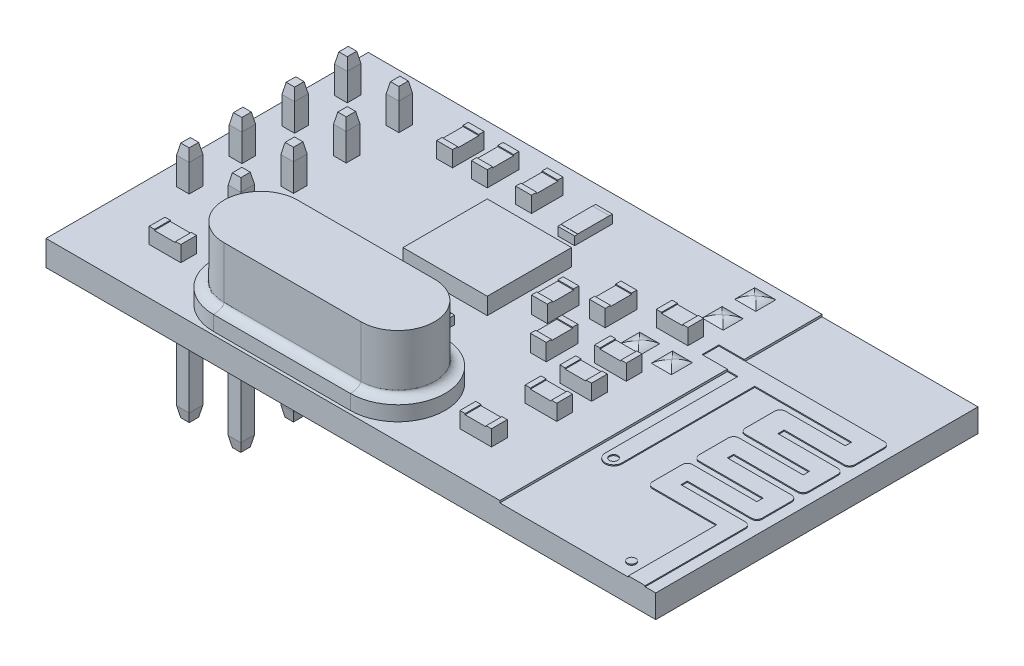
SolidWorks part; units mm, degrees
ref_plane "Plano frontal" through (0, 0, 0) normal (0, 0, 1) x (1, 0, 0)
ref_plane "Plano superior" through (0, 0, 0) normal (0, 1, 0) x (1, 0, 0)
ref_plane "Plano direito" through (0, 0, 0) normal (1, 0, 0) x (0, 0, -1)
sketch "Esboço1" plane through (0, 0, 0) normal (0, 1, 0) x (1, 0, 0)
  line L1 (-14.475, 7.65) -> (14.475, 7.65)
  line L2 (-14.475, 7.65) -> (-14.475, -7.65)
  line L3 (-14.475, -7.65) -> (14.475, -7.65)
  line L4 (14.475, 7.65) -> (14.475, -7.65)
  line L5 (-14.475, 7.65) -> (14.475, -7.65) construction
  line L6 (-14.475, -7.65) -> (14.475, 7.65) construction
  point P0 (0, 0)
  dimension "D1" = 28.95
  dimension "D2" = 15.3
extrude "Ressalto-extrusão1" add sketch "Esboço1" along normal blind 1.2
sketch "Esboço2" plane through (0, 1.2, 0) normal (0, 1, 0) x (1, 0, 0)
  line L0 (-14.475, -7.65) -> (14.475, -7.65) construction
  line L1 (14.475, 7.65) -> (7.075, 7.65)
  line L2 (14.475, 7.65) -> (14.475, -7.65)
  line L3 (14.475, -7.65) -> (7.075, -7.65)
  line L4 (7.075, 7.65) -> (7.075, 3.95)
  line L5 (7.075, 3.95) -> (5.875, 3.95)
  line L6 (5.875, 3.95) -> (5.875, 3.15)
  line L7 (5.875, 3.15) -> (7.075, 3.15)
  line L8 (7.075, 3.15) -> (7.075, -7.65)
  line L9 (14.475, 7.65) -> (-14.475, 7.65) construction
  dimension "D1" = 7.4
  dimension "D2" = 3.7
  dimension "D3" = 0.8
  dimension "D4" = 1.2
extrude "Corte-extrusão1" cut sketch "Esboço2" against normal blind 0.1
sketch "Esboço3" plane through (0, 1.1, 0) normal (0, 1, 0) x (1, 0, 0)
  line L0 (7.075, 3.95) -> (13.975, 3.95)
  line L1 (7.075, 7.65) -> (7.075, 3.95) construction
  line L2 (13.975, 3.95) -> (13.975, 2.05)
  line L3 (13.975, 2.05) -> (10.875, 2.05)
  line L4 (10.875, 2.05) -> (10.875, 1.75)
  line L5 (10.875, 1.75) -> (13.975, 1.75)
  line L6 (13.975, 1.75) -> (13.975, -0.15)
  line L7 (13.975, -0.15) -> (10.675, -0.15)
  line L8 (10.675, -0.15) -> (10.675, -0.45)
  line L9 (10.675, -0.45) -> (13.975, -0.45)
  line L10 (13.975, -0.45) -> (13.975, -2.35)
  line L11 (13.975, -2.35) -> (10.675, -2.35)
  line L12 (10.675, -2.35) -> (10.675, -2.65)
  line L13 (10.675, -2.65) -> (13.975, -2.65)
  line L14 (13.975, -2.65) -> (13.975, -7.65)
  line L15 (7.075, -7.65) -> (14.475, -7.65) construction
  line L16 (13.975, -7.65) -> (13.175, -7.65)
  line L17 (13.175, -7.65) -> (13.175, -3.45)
  line L18 (13.175, -3.45) -> (9.875, -3.45)
  line L19 (9.875, -3.45) -> (9.875, -1.55)
  line L20 (9.875, -1.55) -> (13.175, -1.55)
  line L21 (13.175, -1.55) -> (13.175, -1.25)
  line L22 (13.175, -1.25) -> (9.875, -1.25)
  line L27 (9.875, 0.95) -> (9.875, 2.85)
  line L28 (9.875, 2.85) -> (12.975, 2.85)
  line L29 (12.975, 2.85) -> (12.975, 3.15)
  line L32 (9.875, -1.25) -> (9.875, 0.65)
  line L34 (13.175, 0.65) -> (13.175, 0.95)
  line L35 (7.075, 3.15) -> (7.575, 3.15)
  line L36 (7.575, 3.15) -> (7.575, -3.55)
  line L37 (7.575, -3.55) -> (8.375, -3.55)
  line L38 (8.375, -3.55) -> (8.375, 3.15)
  line L39 (8.375, 3.15) -> (12.975, 3.15)
  line L40 (14.475, 7.65) -> (7.075, 7.65) construction
  line L41 (9.875, 0.65) -> (13.175, 0.65)
  line L42 (9.875, 0.95) -> (13.175, 0.95)
  line L43 (14.475, -7.65) -> (14.475, 7.65) construction
  line L44 (7.075, 7.65) -> (7.075, 3.95) construction
  line L46 (7.075, 3.95) -> (5.875, 3.95)
  line L47 (5.875, 3.95) -> (5.875, 3.15)
  line L48 (5.875, 3.15) -> (7.075, 3.15)
  point P43 (13.175, -1.4)
  dimension "D1" = 3.7
  dimension "D3" = 0.8
  dimension "D4" = 6.7
  dimension "D5" = 0.3
  dimension "D6" = 1.9
  dimension "D7" = 1.9
  dimension "D8" = 0.3
  dimension "D9" = 0.8
  dimension "D10" = 1.9
  dimension "D11" = 0.3
  dimension "D12" = 1.9
  dimension "D13" = 0.3
  dimension "D14" = 0.3
  dimension "D15" = 1.9
  dimension "D16" = 1.9
  dimension "D17" = 0.3
  dimension "D18" = 0.8
  dimension "D19" = 0.5
  dimension "D20" = 0.5
  dimension "D21" = 0.5
  dimension "D22" = 0.5
  dimension "D23" = 1
  dimension "D24" = 0.8
  dimension "D25" = 1
  dimension "D26" = 0.8
  dimension "D27" = 0.8
  dimension "D28" = 0.8
  dimension "D29" = 0.5
  dimension "D30" = 1.5
  dimension "D31" = 1.5
  dimension "D32" = 6.7
extrude "Ressalto-extrusão2" add sketch "Esboço3" along normal blind 0.05
sketch "Esboço4" plane through (0, 1.1, 0) normal (0, 1, 0) x (1, 0, 0)
  line L0 (13.175, -3.45) -> (13.175, -7.65) construction
  line L1 (7.075, -7.65) -> (13.175, -7.65) construction
  circle A0 centre (12.625, -6.95) radius 0.2
  dimension "D1" = 0.4
  dimension "D2" = 0.55
  dimension "D3" = 0.7
extrude "Ressalto-extrusão3" add sketch "Esboço4" along normal blind 0.05
sketch "Esboço5" plane through (0, 1.2, 0) normal (0, 1, 0) x (1, 0, 0)
  line L0 (-6.675, -5.25) -> (-0.175, -5.25) construction
  line L1 (-6.675, -3) -> (-0.175, -3)
  line L2 (-6.675, -7.5) -> (-0.175, -7.5)
  line L3 (-14.475, -7.65) -> (7.075, -7.65) construction
  line L4 (7.075, 3.15) -> (7.075, -7.65) construction
  arc A0 (-6.675, -3) -> (-6.675, -7.5) centre (-6.675, -5.25) ccw
  arc A1 (-0.175, -7.5) -> (-0.175, -3) centre (-0.175, -5.25) ccw
  point P2 (-3.425, -5.25)
  dimension "D3" = 6.5
  dimension "D4" = 7.25
  dimension "D1" = 4.5
  dimension "D2" = 0.15
extrude "Ressalto-extrusão4" add sketch "Esboço5" along normal blind 0.7
sketch "Esboço6" plane through (0, 1.9, 0) normal (0, 1, 0) x (1, 0, 0)
  line L0 (-6.675, -5.25) -> (-0.175, -5.25) construction
  line L1 (-6.675, -3.5) -> (-0.175, -3.5)
  line L2 (-6.675, -7) -> (-0.175, -7)
  line L3 (-6.675, -7.5) -> (-0.175, -7.5) construction
  arc A0 (-6.675, -3.5) -> (-6.675, -7) centre (-6.675, -5.25) ccw
  arc A1 (-0.175, -7) -> (-0.175, -3.5) centre (-0.175, -5.25) ccw
  arc A4 (-6.675, -3) -> (-6.675, -7.5) centre (-6.675, -5.25) ccw construction
  point P2 (-3.425, -5.25)
  point P9 (-3.425, -7.5)
  point P13 (-8.925, -5.25)
  dimension "D2" = 3.5
  dimension "D3" = 0.5
  dimension "D4" = 2.25
  dimension "D1" = 6.5
extrude "Ressalto-extrusão5" add sketch "Esboço6" along normal blind 2.7
sketch "Esboço7" plane through (0, 1.15, 0) normal (0, 1, 0) x (1, 0, 0)
  line L0 (7.575, -3.15) -> (7.575, -3.55)
  line L1 (7.575, -3.55) -> (7.975, -3.55)
  line L2 (7.975, -3.55) -> (8.375, -3.55)
  line L3 (8.375, -3.55) -> (8.375, -3.15)
  arc A0 (7.575, -3.15) -> (8.375, -3.15) centre (7.975, -3.15) ccw
  line M7 (7.575, 3.15) -> (7.575, -3.55)
  line M8 (7.575, -3.55) -> (8.375, -3.55)
  line M9 (8.375, -3.55) -> (8.375, 3.15)
extrude "Corte-extrusão2" cut sketch "Esboço7" against normal blind 0.05 contours A0 M8 M9 | A0 M7 M8
sketch "Esboço8" plane through (0, 1.15, 0) normal (0, 1, 0) x (1, 0, 0)
  circle A0 centre (7.975, -3.15) radius 0.2
  dimension "D1" = 0.4
extrude "Corte-extrusão3" cut sketch "Esboço8" against normal blind 0.05
sketch "Esboço9" plane through (0, 1.2, 0) normal (0, 1, 0) x (1, 0, 0)
  line L0 (-14.475, -7.65) -> (7.075, -7.65) construction
  line L1 (-11.775, -4.7) -> (-10.275, -4.7)
  line L2 (-11.775, -4.7) -> (-11.775, -5.45)
  line L3 (-11.775, -5.45) -> (-10.275, -5.45)
  line L4 (-10.275, -4.7) -> (-10.275, -5.45)
  line L5 (-14.475, 7.65) -> (-14.475, -7.65) construction
  line L6 (7.075, 7.65) -> (-14.475, 7.65) construction
  line L7 (5.875, 3.95) -> (5.875, 3.15) construction
  line L8 (3.175, -4.9) -> (4.675, -4.9)
  line L9 (3.175, -4.9) -> (3.175, -5.65)
  line L10 (3.175, -5.65) -> (4.675, -5.65)
  line L11 (4.675, -4.9) -> (4.675, -5.65)
  line L12 (3.675, -2.3) -> (5.175, -2.3)
  line L13 (3.675, -2.3) -> (3.675, -3.05)
  line L14 (3.675, -3.05) -> (5.175, -3.05)
  line L15 (5.175, -2.3) -> (5.175, -3.05)
  line L16 (3.675, -0.65) -> (5.175, -0.65)
  line L17 (3.675, -0.65) -> (3.675, -1.4)
  line L18 (3.675, -1.4) -> (5.175, -1.4)
  line L19 (5.175, -0.65) -> (5.175, -1.4)
  line L20 (3.675, 1) -> (5.175, 1)
  line L21 (3.675, 1) -> (3.675, 0.25)
  line L22 (3.675, 0.25) -> (5.175, 0.25)
  line L23 (5.175, 1) -> (5.175, 0.25)
  line L24 (3.675, 3.925) -> (5.175, 3.925)
  line L25 (3.675, 3.925) -> (3.675, 3.175)
  line L26 (3.675, 3.175) -> (5.175, 3.175)
  line L27 (5.175, 3.925) -> (5.175, 3.175)
  line L33 (7.075, 3.95) -> (5.875, 3.95) construction
  line L35 (-8.475, 6.4) -> (-7.725, 6.4)
  line L36 (-8.475, 6.4) -> (-8.475, 4.9)
  line L37 (-8.475, 4.9) -> (-7.725, 4.9)
  line L38 (-7.725, 6.4) -> (-7.725, 4.9)
  line L39 (-6.825, 6.4) -> (-6.075, 6.4)
  line L40 (-6.825, 6.4) -> (-6.825, 4.9)
  line L41 (-6.825, 4.9) -> (-6.075, 4.9)
  line L42 (-6.075, 6.4) -> (-6.075, 4.9)
  line L43 (-4.725, 6.4) -> (-3.975, 6.4)
  line L44 (-4.725, 6.4) -> (-4.725, 4.9)
  line L45 (-4.725, 4.9) -> (-3.975, 4.9)
  line L46 (-3.975, 6.4) -> (-3.975, 4.9)
  arc A0 (-6.675, -3) -> (-6.675, -7.5) centre (-6.675, -5.25) ccw construction
  arc A1 (-0.175, -7.5) -> (-0.175, -3) centre (-0.175, -5.25) ccw construction
  point P9 (-8.925, -5.25)
  point P17 (2.075, -5.25)
  point P52 (-6.45, 6.4)
  dimension "D1" = 1.5
  dimension "D2" = 2.2
  dimension "D3" = 1.35
  dimension "D4" = 0.75
  dimension "D5" = 1.5
  dimension "D6" = 0.75
  dimension "D7" = 1.1
  dimension "D8" = 2
  dimension "D9" = 1.85
  dimension "D10" = 0.75
  dimension "D11" = 1.5
  dimension "D12" = 0.9
  dimension "D13" = 0.9
  dimension "D14" = 0.75
  dimension "D15" = 0.75
  dimension "D16" = 1.5
  dimension "D17" = 1.5
  dimension "D18" = 0.75
  dimension "D19" = 1.5
  dimension "D20" = 0.7
  dimension "D21" = 0
  dimension "D22" = 0
  dimension "D23" = 0
  dimension "D24" = 0.025
  dimension "D25" = 0.75
  dimension "D26" = 0.75
  dimension "D27" = 0.75
  dimension "D28" = 1.5
  dimension "D29" = 1.5
  dimension "D30" = 1.5
  dimension "D31" = 6
  dimension "D32" = 0.9
  dimension "D33" = 1.35
  dimension "D34" = 0
  dimension "D35" = 1.25
  dimension "D36" = 1.25
extrude "Ressalto-extrusão6" add sketch "Esboço9" along normal blind 0.75
fillet "Filete1" radius 0.5 4 edges at (-3.425, 1.9, 3.5) (-8.425, 1.9, 5.25) (1.575, 1.9, 5.25) (-3.425, 1.9, 7)
sketch "Esboço10" plane through (0, 0, 0) normal (0, -1, 0) x (1, 0, 0)
  line L0 (-14.475, -7.65) -> (-14.475, 7.65) construction
  line L1 (-14.475, -6.65) -> (-9.475, -6.65)
  line L2 (-14.475, -6.65) -> (-14.475, -4.15)
  line L3 (-14.475, -4.15) -> (-9.475, -4.15)
  line L4 (-9.475, -6.65) -> (-9.475, -4.15)
  line L5 (14.475, -7.65) -> (-14.475, -7.65) construction
  dimension "D1" = 5
  dimension "D2" = 2.5
  dimension "D3" = 1
extrude "Ressalto-extrusão7" add sketch "Esboço10" along normal blind 2.6
chamfer "Chanfro2" distance 0.7092 angle 45 2 edges at (-14.475, -1.3, -4.15) (-9.475, -1.3, -4.15)
sketch "Esboço11" plane through (0, 0, 0) normal (0, -1, 0) x (1, 0, 0)
  line L0 (-14.475, -4.8592) -> (-14.475, 7.65) construction
  line L1 (-14.475, -4.15) -> (-9.475, -4.15)
  line L2 (-14.475, -4.15) -> (-14.475, -1.65)
  line L3 (-14.475, -1.65) -> (-9.475, -1.65)
  line L4 (-9.475, -4.15) -> (-9.475, -1.65)
  dimension "D1" = 2.5
  dimension "D2" = 5
extrude "Ressalto-extrusão8" add sketch "Esboço11" along normal blind 2.6
chamfer "Chanfro3" distance 0.7092 angle 45 2 edges at (-9.475, -1.3, -1.65) (-14.475, -1.3, -1.65)
sketch "Esboço12" plane through (0, 0, 0) normal (0, -1, 0) x (1, 0, 0)
  line L0 (-14.475, -2.3592) -> (-14.475, 7.65) construction
  line L1 (-14.475, -1.65) -> (-9.475, -1.65)
  line L2 (-14.475, -1.65) -> (-14.475, 0.85)
  line L3 (-14.475, 0.85) -> (-9.475, 0.85)
  line L4 (-9.475, -1.65) -> (-9.475, 0.85)
  dimension "D1" = 2.5
  dimension "D2" = 5
extrude "Ressalto-extrusão9" add sketch "Esboço12" along normal blind 2.6
chamfer "Chanfro4" distance 0.7092 angle 45 2 edges at (-9.475, -1.3, 0.85) (-14.475, -1.3, 0.85)
sketch "Esboço13" plane through (0, 0, 0) normal (0, -1, 0) x (1, 0, 0)
  line L0 (-14.475, 0.1408) -> (-14.475, 7.65) construction
  line L1 (-14.475, 0.85) -> (-9.475, 0.85)
  line L2 (-14.475, 0.85) -> (-14.475, 3.35)
  line L3 (-14.475, 3.35) -> (-9.475, 3.35)
  line L4 (-9.475, 0.85) -> (-9.475, 3.35)
  dimension "D1" = 2.5
  dimension "D2" = 5
extrude "Ressalto-extrusão10" add sketch "Esboço13" along normal blind 2.6
chamfer "Chanfro5" distance 0.7092 angle 45 10 edges at (-9.475, -1.3, -6.65) (-14.475, -1.3, -6.65) (-9.475, -1.3, -4.15) (-14.475, -1.3, -4.15) (-9.475, -1.3, -1.65) (-14.475, -1.3, -1.65) (-14.475, -1.3, 0.85) (-9.475, -1.3, 0.85) (-9.475, -1.3, 3.35) (-14.475, -1.3, 3.35)
sketch "Esboço14" plane through (0, -2.6, 0) normal (0, -1, 0) x (1, 0, 0)
  line L0 (-14.475, 2.6408) -> (-14.475, 1.5592) construction
  line L1 (-13.5, 2.425) -> (-12.9, 2.425)
  line L2 (-13.5, 2.425) -> (-13.5, 1.775)
  line L3 (-13.5, 1.775) -> (-12.9, 1.775)
  line L4 (-12.9, 2.425) -> (-12.9, 1.775)
  line L5 (-11.05, 2.425) -> (-10.45, 2.425)
  line L6 (-11.05, 2.425) -> (-11.05, 1.775)
  line L7 (-11.05, 1.775) -> (-10.45, 1.775)
  line L8 (-10.45, 2.425) -> (-10.45, 1.775)
  line L9 (-13.5, -0.075) -> (-12.9, -0.075)
  line L10 (-13.5, -0.075) -> (-13.5, -0.725)
  line L11 (-13.5, -0.725) -> (-12.9, -0.725)
  line L12 (-12.9, -0.075) -> (-12.9, -0.725)
  line L13 (-11.05, -0.075) -> (-10.45, -0.075)
  line L14 (-11.05, -0.075) -> (-11.05, -0.725)
  line L15 (-11.05, -0.725) -> (-10.45, -0.725)
  line L16 (-10.45, -0.075) -> (-10.45, -0.725)
  line L17 (-13.497, -2.575) -> (-12.897, -2.575)
  line L18 (-13.497, -2.575) -> (-13.497, -3.225)
  line L19 (-13.497, -3.225) -> (-12.897, -3.225)
  line L20 (-12.897, -2.575) -> (-12.897, -3.225)
  line L21 (-11.047, -2.575) -> (-10.447, -2.575)
  line L22 (-11.047, -2.575) -> (-11.047, -3.225)
  line L23 (-11.047, -3.225) -> (-10.447, -3.225)
  line L24 (-10.447, -2.575) -> (-10.447, -3.225)
  line L25 (-13.497, -5.075) -> (-12.897, -5.075)
  line L26 (-13.497, -5.075) -> (-13.497, -5.725)
  line L27 (-13.497, -5.725) -> (-12.897, -5.725)
  line L28 (-12.897, -5.075) -> (-12.897, -5.725)
  line L29 (-11.047, -5.075) -> (-10.447, -5.075)
  line L30 (-11.047, -5.075) -> (-11.047, -5.725)
  line L31 (-11.047, -5.725) -> (-10.447, -5.725)
  line L32 (-10.447, -5.075) -> (-10.447, -5.725)
  line L33 (-14.475, 0.1408) -> (-14.475, -0.9408) construction
  line L34 (-10.1842, 3.35) -> (-13.7658, 3.35) construction
  line L35 (-10.1842, 3.35) -> (-13.7658, 3.35) construction
  line L36 (-14.475, -2.3592) -> (-14.475, -3.4408) construction
  line L37 (-14.475, -4.8592) -> (-14.475, -5.9408) construction
  dimension "D1" = 0.6
  dimension "D2" = 0.6
  dimension "D3" = 0.65
  dimension "D4" = 0.65
  dimension "D5" = 1.85
  dimension "D6" = 0.975
  dimension "D7" = 0.975
  dimension "D8" = 1.85
  dimension "D9" = 0.6
  dimension "D10" = 0.6
  dimension "D11" = 0.65
  dimension "D12" = 0.65
  dimension "D13" = 0.925
  dimension "D14" = 0.925
  dimension "D15" = 1.85
  dimension "D16" = 1.85
  dimension "D17" = 1.85
  dimension "D18" = 1.85
  dimension "D19" = 1.85
  dimension "D20" = 1.85
  dimension "D21" = 0.6
  dimension "D22" = 0.65
  dimension "D23" = 0.6
  dimension "D24" = 0.65
  dimension "D25" = 0.6
  dimension "D26" = 0.65
  dimension "D27" = 0.6
  dimension "D28" = 0.65
  dimension "D29" = 1.85
  dimension "D30" = 1.85
  dimension "D31" = 0.978
  dimension "D32" = 0.978
sketch "Esboço15" plane through (0, 1.2, 0) normal (0, 1, 0) x (1, 0, 0)
  line L1 (-0.825, -0.35) -> (-4.825, -0.35)
  line L2 (-0.825, -0.35) -> (-0.825, 3.65)
  line L3 (-0.825, 3.65) -> (-4.825, 3.65)
  line L4 (-4.825, -0.35) -> (-4.825, 3.65)
  line L6 (-4.725, 4.9) -> (-3.975, 4.9) construction
  line L7 (3.675, 1) -> (3.675, 0.25) construction
  dimension "D1" = 4
  dimension "D2" = 4
  dimension "D3" = 1.25
  dimension "D4" = 4.5
extrude "Ressalto-extrusão12" add sketch "Esboço15" along normal blind 0.8
sketch "Esboço16" plane through (0, 1.2, 0) normal (0, 1, 0) x (1, 0, 0)
  line L0 (3.675, -0.65) -> (3.675, -1.4) construction
  line L1 (-1.225, -2.3) -> (-3.025, -2.3)
  line L2 (-1.225, -2.3) -> (-1.225, -1.5)
  line L3 (-1.225, -1.5) -> (-3.025, -1.5)
  line L4 (-3.025, -2.3) -> (-3.025, -1.5)
  line L5 (-4.825, -0.35) -> (-0.825, -0.35) construction
  line L7 (-1.625, 4.6) -> (-2.425, 4.6)
  line L8 (-1.625, 4.6) -> (-1.625, 6.4)
  line L9 (-1.625, 6.4) -> (-2.425, 6.4)
  line L10 (-2.425, 4.6) -> (-2.425, 6.4)
  line L11 (-3.975, 6.4) -> (-4.725, 6.4) construction
  line L12 (-3.975, 4.9) -> (-3.975, 6.4) construction
  dimension "D1" = 0.8
  dimension "D2" = 1.8
  dimension "D3" = 4.9
  dimension "D4" = 1.15
  dimension "D5" = 0.8
  dimension "D6" = 1.8
  dimension "D7" = 0
  dimension "D8" = 1.55
extrude "Ressalto-extrusão13" add sketch "Esboço16" along normal blind 0.4
sketch "Esboço17" plane through (0, 1.2, 0) normal (0, 1, 0) x (1, 0, 0)
  line L0 (3.675, -0.65) -> (3.675, -1.4) construction
  line L1 (0.925, 0.75) -> (0.175, 0.75)
  line L2 (0.925, 0.75) -> (0.925, 2.25)
  line L3 (0.925, 2.25) -> (0.175, 2.25)
  line L4 (0.175, 0.75) -> (0.175, 2.25)
  line L5 (2.475, -0.85) -> (1.725, -0.85)
  line L6 (2.475, -0.85) -> (2.475, 0.65)
  line L7 (2.475, 0.65) -> (1.725, 0.65)
  line L8 (1.725, -0.85) -> (1.725, 0.65)
  line L9 (2.475, 1.95) -> (1.725, 1.95)
  line L10 (2.475, 1.95) -> (2.475, 3.45)
  line L11 (2.475, 3.45) -> (1.725, 3.45)
  line L12 (1.725, 1.95) -> (1.725, 3.45)
  line L13 (3.675, 3.925) -> (3.675, 3.175) construction
  line L14 (7.075, 7.65) -> (-14.475, 7.65) construction
  line L15 (-0.825, -0.35) -> (-0.825, 3.65) construction
  point P20 (0.55, 2.25)
  dimension "D1" = 0.75
  dimension "D2" = 0.75
  dimension "D3" = 0.75
  dimension "D4" = 1.5
  dimension "D5" = 1.5
  dimension "D6" = 1.5
  dimension "D7" = 1.3
  dimension "D8" = 1.2
  dimension "D9" = 1.2
  dimension "D10" = 4.2
  dimension "D11" = 1
  dimension "D12" = 5.4
extrude "Ressalto-extrusão14" add sketch "Esboço17" along normal blind 0.8
sketch "Esboço18" plane through (0, 2, 0) normal (0, 1, 0) x (1, 0, 0)
  line L0 (2.475, -0.85) -> (2.475, 0.65) construction
  line L1 (2.475, -0.6) -> (1.725, -0.6)
  line L2 (2.475, -0.6) -> (2.475, 0.4)
  line L3 (2.475, 0.4) -> (1.725, 0.4)
  line L4 (1.725, -0.6) -> (1.725, 0.4)
  line L5 (1.725, 0.65) -> (1.725, -0.85) construction
  line L6 (0.925, 0.75) -> (0.925, 2.25) construction
  line L7 (0.925, 1) -> (0.175, 1)
  line L8 (0.925, 1) -> (0.925, 2)
  line L9 (0.925, 2) -> (0.175, 2)
  line L10 (0.175, 1) -> (0.175, 2)
  line L11 (0.175, 2.25) -> (0.175, 0.75) construction
  line L12 (2.475, 1.95) -> (2.475, 3.45) construction
  line L13 (2.475, 2.2) -> (1.725, 2.2)
  line L14 (2.475, 2.2) -> (2.475, 3.2)
  line L15 (2.475, 3.2) -> (1.725, 3.2)
  line L16 (1.725, 2.2) -> (1.725, 3.2)
  line L17 (1.725, 3.45) -> (1.725, 1.95) construction
  line L18 (1.725, -0.85) -> (2.475, -0.85) construction
  line L20 (0.175, 0.75) -> (0.925, 0.75) construction
  line L21 (2.475, 3.45) -> (1.725, 3.45) construction
  dimension "D1" = 1
  dimension "D2" = 0.25
  dimension "D3" = 0.25
  dimension "D4" = 1
  dimension "D5" = 1
  dimension "D6" = 0.25
extrude "Corte-extrusão4" cut sketch "Esboço18" against normal blind 0.05
sketch "Esboço19" plane through (0, 1.95, 0) normal (0, 1, 0) x (1, 0, 0)
  line L0 (-3.975, 4.9) -> (-3.975, 6.4) construction
  line L1 (-3.975, 5.15) -> (-4.725, 5.15)
  line L2 (-3.975, 5.15) -> (-3.975, 6.15)
  line L3 (-3.975, 6.15) -> (-4.725, 6.15)
  line L4 (-4.725, 5.15) -> (-4.725, 6.15)
  line L5 (-4.725, 6.4) -> (-4.725, 4.9) construction
  line L6 (-6.075, 4.9) -> (-6.075, 6.4) construction
  line L7 (-6.075, 5.15) -> (-6.825, 5.15)
  line L8 (-6.075, 5.15) -> (-6.075, 6.15)
  line L9 (-6.075, 6.15) -> (-6.825, 6.15)
  line L10 (-6.825, 5.15) -> (-6.825, 6.15)
  line L11 (-6.825, 6.4) -> (-6.825, 4.9) construction
  line L12 (-7.725, 4.9) -> (-7.725, 6.4) construction
  line L13 (-7.725, 5.15) -> (-8.475, 5.15)
  line L14 (-7.725, 5.15) -> (-7.725, 6.15)
  line L15 (-7.725, 6.15) -> (-8.475, 6.15)
  line L16 (-8.475, 5.15) -> (-8.475, 6.15)
  line L17 (-8.475, 6.4) -> (-8.475, 4.9) construction
  line L18 (3.675, 3.175) -> (5.175, 3.175) construction
  line L19 (4.925, 3.175) -> (3.925, 3.175)
  line L20 (4.925, 3.175) -> (4.925, 3.925)
  line L21 (4.925, 3.925) -> (3.925, 3.925)
  line L22 (3.925, 3.175) -> (3.925, 3.925)
  line L23 (5.175, 3.925) -> (3.675, 3.925) construction
  line L24 (3.675, 0.25) -> (5.175, 0.25) construction
  line L25 (4.925, 0.25) -> (3.925, 0.25)
  line L26 (4.925, 0.25) -> (4.925, 1)
  line L27 (4.925, 1) -> (3.925, 1)
  line L28 (3.925, 0.25) -> (3.925, 1)
  line L29 (5.175, 1) -> (3.675, 1) construction
  line L30 (3.675, -1.4) -> (5.175, -1.4) construction
  line L31 (4.925, -1.4) -> (3.925, -1.4)
  line L32 (4.925, -1.4) -> (4.925, -0.65)
  line L33 (4.925, -0.65) -> (3.925, -0.65)
  line L34 (3.925, -1.4) -> (3.925, -0.65)
  line L35 (5.175, -0.65) -> (3.675, -0.65) construction
  line L36 (3.675, -3.05) -> (5.175, -3.05) construction
  line L37 (4.925, -3.05) -> (3.925, -3.05)
  line L38 (4.925, -3.05) -> (4.925, -2.3)
  line L39 (4.925, -2.3) -> (3.925, -2.3)
  line L40 (3.925, -3.05) -> (3.925, -2.3)
  line L41 (5.175, -2.3) -> (3.675, -2.3) construction
  line L42 (3.175, -5.65) -> (4.675, -5.65) construction
  line L43 (4.425, -5.65) -> (3.425, -5.65)
  line L44 (4.425, -5.65) -> (4.425, -4.9)
  line L45 (4.425, -4.9) -> (3.425, -4.9)
  line L46 (3.425, -5.65) -> (3.425, -4.9)
  line L47 (4.675, -4.9) -> (3.175, -4.9) construction
  line L48 (-11.775, -5.45) -> (-10.275, -5.45) construction
  line L49 (-10.525, -5.45) -> (-11.525, -5.45)
  line L50 (-10.525, -5.45) -> (-10.525, -4.7)
  line L51 (-10.525, -4.7) -> (-11.525, -4.7)
  line L52 (-11.525, -5.45) -> (-11.525, -4.7)
  line L53 (-10.275, -4.7) -> (-11.775, -4.7) construction
  line L54 (-11.775, -4.7) -> (-11.775, -5.45) construction
  line L55 (3.175, -4.9) -> (3.175, -5.65) construction
  line L56 (3.675, -2.3) -> (3.675, -3.05) construction
  line L57 (3.675, -0.65) -> (3.675, -1.4) construction
  line L58 (5.175, 0.25) -> (5.175, 1) construction
  line L59 (5.175, 3.175) -> (5.175, 3.925) construction
  line L60 (-4.725, 4.9) -> (-3.975, 4.9) construction
  line L61 (-6.825, 4.9) -> (-6.075, 4.9) construction
  line L62 (-8.475, 4.9) -> (-7.725, 4.9) construction
  dimension "D1" = 1
  dimension "D2" = 0.25
  dimension "D3" = 0.25
  dimension "D4" = 1
  dimension "D5" = 1
  dimension "D6" = 0.25
  dimension "D7" = 1
  dimension "D8" = 0.25
  dimension "D9" = 0.25
  dimension "D10" = 1
  dimension "D11" = 1
  dimension "D12" = 0.25
  dimension "D13" = 0.25
  dimension "D14" = 1
  dimension "D15" = 1
  dimension "D16" = 0.25
  dimension "D17" = 0.25
  dimension "D18" = 1
extrude "Corte-extrusão5" cut sketch "Esboço19" against normal blind 0.05
sketch "Esboço20" plane through (0, 1.6, 0) normal (0, 1, 0) x (1, 0, 0)
  line L0 (-3.025, -2.3) -> (-1.225, -2.3) construction
  line L1 (-1.375, -2.3) -> (-2.875, -2.3)
  line L2 (-1.375, -2.3) -> (-1.375, -1.5)
  line L3 (-1.375, -1.5) -> (-2.875, -1.5)
  line L4 (-2.875, -2.3) -> (-2.875, -1.5)
  line L5 (-1.225, -1.5) -> (-3.025, -1.5) construction
  line L6 (-1.625, 4.6) -> (-1.625, 6.4) construction
  line L7 (-1.625, 4.75) -> (-2.425, 4.75)
  line L8 (-1.625, 4.75) -> (-1.625, 6.25)
  line L9 (-1.625, 6.25) -> (-2.425, 6.25)
  line L10 (-2.425, 4.75) -> (-2.425, 6.25)
  line L11 (-2.425, 6.4) -> (-2.425, 4.6) construction
  line L13 (-3.025, -1.5) -> (-3.025, -2.3) construction
  line L14 (-2.425, 4.6) -> (-1.625, 4.6) construction
  dimension "D1" = 1.5
  dimension "D2" = 0.15
  dimension "D3" = 1.5
  dimension "D4" = 0.15
extrude "Ressalto-extrusão15" add sketch "Esboço20" along normal blind 0.01
sketch "Esboço21" plane through (-14.475, 0, 0) normal (-1, 0, 0) x (0, 0, 1)
  line L1 (2.6408, 0) -> (1.5592, 0)
  line L2 (2.6408, 0) -> (2.6408, -2.6)
  line L3 (2.6408, -2.6) -> (1.5592, -2.6)
  line L4 (1.5592, 0) -> (1.5592, -2.6)
  line L5 (0.1408, 0) -> (-0.9408, 0)
  line L6 (0.1408, 0) -> (0.1408, -2.6)
  line L7 (0.1408, -2.6) -> (-0.9408, -2.6)
  line L8 (-0.9408, 0) -> (-0.9408, -2.6)
  line L9 (-2.3592, 0) -> (-3.4408, 0)
  line L10 (-2.3592, 0) -> (-2.3592, -2.6)
  line L11 (-2.3592, -2.6) -> (-3.4408, -2.6)
  line L12 (-3.4408, 0) -> (-3.4408, -2.6)
  line L13 (-4.8592, 0) -> (-5.9408, 0)
  line L14 (-4.8592, 0) -> (-4.8592, -2.6)
  line L15 (-4.8592, -2.6) -> (-5.9408, -2.6)
  line L16 (-5.9408, 0) -> (-5.9408, -2.6)
extrude "Corte-extrusão6" cut sketch "Esboço21" against normal blind 0.001
sketch "Esboço22" plane through (0, 0, -6.65) normal (0, 0, -1) x (-1, 0, 0)
  line L0 (13.7658, 0) -> (10.1842, 0) construction
  line L1 (13.4742, 0) -> (10.4742, 0)
  line L2 (13.4742, 0) -> (13.4742, -1)
  line L3 (13.4742, -1) -> (10.4742, -1)
  line L4 (10.4742, 0) -> (10.4742, -1)
  line L5 (10.1842, 0) -> (10.1842, -2.6) construction
  dimension "D1" = 3
  dimension "D2" = 1
  dimension "D3" = 0.29
extrude "Corte-extrusão7" cut sketch "Esboço22" against normal through all
extrude "Ressalto-extrusão16" add sketch "Esboço14" along normal blind 5.7 and the other way blind 5.6
chamfer "Chanfro8" distance 0.5 distance2 0.1 32 edges at (-10.75, -8.3, 2.425) (-10.45, -8.3, 2.1) (-10.75, -8.3, 1.775) (-11.05, -8.3, 2.1) (-13.2, -8.3, 2.425) (-12.9, -8.3, 2.1) (-13.2, -8.3, 1.775) (-13.5, -8.3, 2.1) (-13.2, -8.3, -0.075) (-12.9, -8.3, -0.4) (-13.2, -8.3, -0.725) (-13.5, -8.3, -0.4) (-10.75, -8.3, -0.075) (-10.45, -8.3, -0.4) (-10.75, -8.3, -0.725) (-11.05, -8.3, -0.4) (-10.747, -8.3, -2.575) (-10.447, -8.3, -2.9) (-10.747, -8.3, -3.225) (-11.047, -8.3, -2.9) (-13.197, -8.3, -2.575) (-12.897, -8.3, -2.9) (-13.197, -8.3, -3.225) (-13.497, -8.3, -2.9) (-10.747, -8.3, -5.075) (-10.447, -8.3, -5.4) (-10.747, -8.3, -5.725) (-11.047, -8.3, -5.4) (-13.197, -8.3, -5.075) (-12.897, -8.3, -5.4) (-13.197, -8.3, -5.725) (-13.497, -8.3, -5.4)
chamfer "Chanfro9" distance 0.1 distance2 0.5 32 edges at (-10.747, 3, -3.225) (-10.447, 3, -2.9) (-10.747, 3, -2.575) (-11.047, 3, -2.9) (-13.197, 3, -3.225) (-12.897, 3, -2.9) (-13.197, 3, -2.575) (-13.497, 3, -2.9) (-13.197, 3, -5.725) (-12.897, 3, -5.4) (-13.197, 3, -5.075) (-13.497, 3, -5.4) (-10.747, 3, -5.725) (-10.447, 3, -5.4) (-10.747, 3, -5.075) (-11.047, 3, -5.4) (-13.2, 3, -0.725) (-12.9, 3, -0.4) (-13.2, 3, -0.075) (-13.5, 3, -0.4) (-10.75, 3, -0.725) (-10.45, 3, -0.4) (-10.75, 3, -0.075) (-11.05, 3, -0.4) (-10.75, 3, 1.775) (-10.45, 3, 2.1) (-10.75, 3, 2.425) (-11.05, 3, 2.1) (-13.2, 3, 1.775) (-12.9, 3, 2.1) (-13.2, 3, 2.425) (-13.5, 3, 2.1)
sketch "Esboço23" plane through (0, 1.2, 0) normal (0, 1, 0) x (1, 0, 0)
  line L0 (7.075, 7.65) -> (-14.475, 7.65) construction
  line L1 (4.375, 7.15) -> (5.375, 7.15)
  line L2 (4.375, 7.15) -> (4.375, 6.2)
  line L3 (4.375, 6.2) -> (5.375, 6.2)
  line L4 (5.375, 7.15) -> (5.375, 6.2)
  line L5 (4.375, 5.6) -> (5.375, 5.6)
  line L6 (4.375, 5.6) -> (4.375, 4.65)
  line L7 (4.375, 4.65) -> (5.375, 4.65)
  line L8 (5.375, 5.6) -> (5.375, 4.65)
  line L9 (-1.625, 4.6) -> (-1.625, 6.4) construction
  line L10 (5.175, 1) -> (3.675, 1) construction
  line L11 (3.475, 2.59) -> (4.425, 2.59)
  line L12 (3.475, 2.59) -> (3.475, 1.59)
  line L13 (3.475, 1.59) -> (4.425, 1.59)
  line L14 (4.425, 2.59) -> (4.425, 1.59)
  line L15 (5.025, 2.59) -> (5.975, 2.59)
  line L16 (5.025, 2.59) -> (5.025, 1.59)
  line L17 (5.025, 1.59) -> (5.975, 1.59)
  line L18 (5.975, 2.59) -> (5.975, 1.59)
  line L20 (2.475, 1.95) -> (2.475, 3.45) construction
  dimension "D1" = 0.5
  dimension "D2" = 0.95
  dimension "D3" = 1
  dimension "D4" = 6
  dimension "D5" = 0.6
  dimension "D6" = 0.95
  dimension "D7" = 1
  dimension "D8" = 0
  dimension "D9" = 0.95
  dimension "D10" = 1
  dimension "D11" = 1
  dimension "D12" = 0.95
  dimension "D13" = 0.6
  dimension "D14" = 0.59
  dimension "D15" = 1
  dimension "D16" = 0.59
extrude "Ressalto-extrusão17" add sketch "Esboço23" along normal blind 0.15
fillet "Filete2" radius 0.75 16 edges at (4.875, 1.35, -5.6) (5.375, 1.35, -5.125) (4.875, 1.35, -4.65) (4.375, 1.35, -5.125) (4.875, 1.35, -7.15) (5.375, 1.35, -6.675) (4.875, 1.35, -6.2) (4.375, 1.35, -6.675) (5.5, 1.35, -2.59) (5.975, 1.35, -2.09) (5.5, 1.35, -1.59) (5.025, 1.35, -2.09) (3.95, 1.35, -2.59) (4.425, 1.35, -2.09) (3.95, 1.35, -1.59) (3.475, 1.35, -2.09)
fillet "Filete3" radius 0.25 13 edges at (13.975, 1.125, -2.05) (9.875, 1.125, -0.95) (13.975, 1.125, 0.15) (13.975, 1.125, 2.35) (9.875, 1.125, 1.25) (9.875, 1.125, 3.45) (13.975, 1.125, 2.65) (9.875, 1.125, 1.55) (9.875, 1.125, -0.65) (13.975, 1.125, 0.45) (13.975, 1.125, -1.75) (13.975, 1.125, -3.95) (9.875, 1.125, -2.85)
